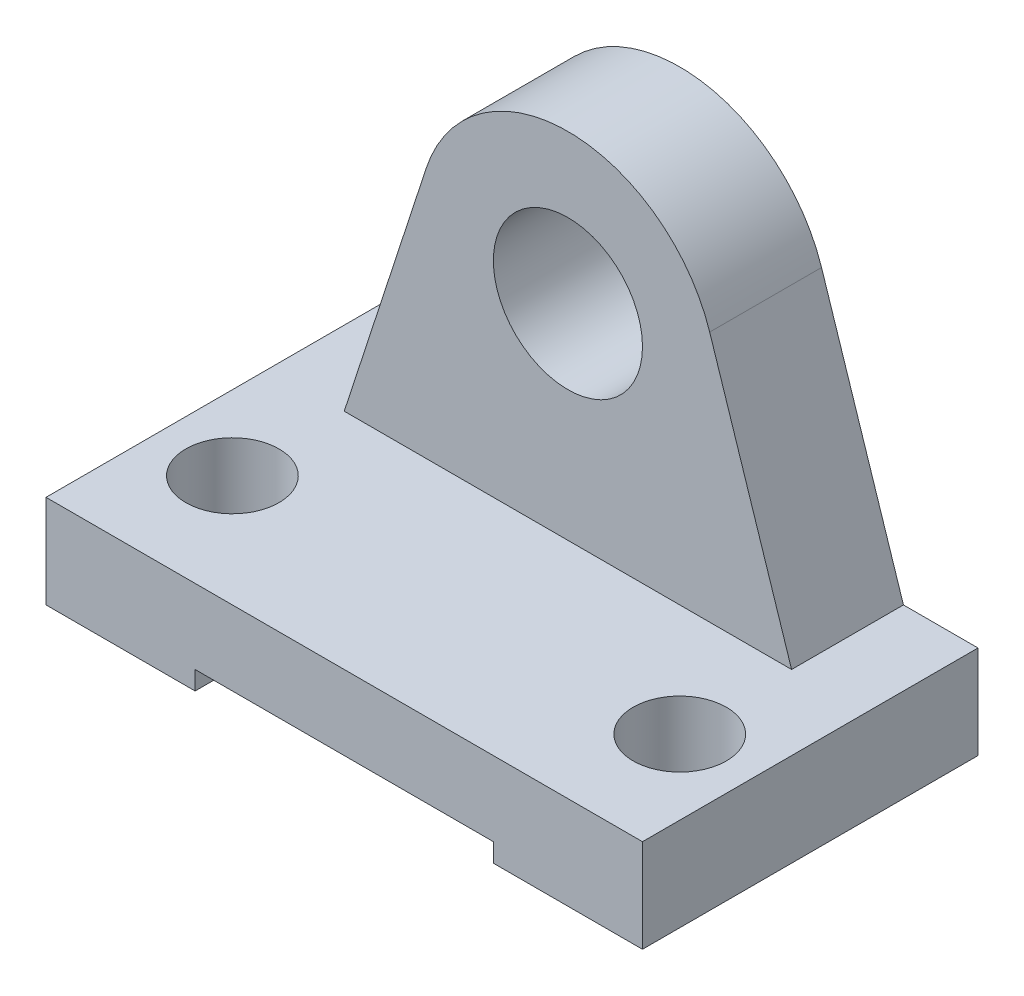
SolidWorks part; units mm, degrees
ref_plane "前视基准面" through (0, 0, 0) normal (0, 0, 1) x (1, 0, 0)
ref_plane "上视基准面" through (0, 0, 0) normal (0, 1, 0) x (1, 0, 0)
ref_plane "右视基准面" through (0, 0, 0) normal (1, 0, 0) x (0, 0, -1)
other "Configuration Table"
sketch "草图1" plane through (0, 0, 0) normal (0, 0, 1) x (1, 0, 0)
  line L0 (-415.6693, 0) -> (20367.7972, 0) construction
  line L1 (0, -415.6693) -> (0, 20367.7972) construction
  line L2 (8, 0) -> (-8, 0)
  line L3 (-8, 0) -> (-8, -1)
  line L4 (-8, -1) -> (-16, -1)
  line L5 (-16, -1) -> (-16, 4)
  line L6 (-16, 4) -> (16, 4)
  line L7 (-12, 4) -> (-7.6061, 17.4794)
  line L8 (16, -1) -> (16, 4)
  line L9 (8, -1) -> (16, -1)
  line L10 (12, 4) -> (7.6061, 17.4794)
  line L11 (8, 0) -> (8, -1)
  arc A0 (-7.6061, 17.4794) -> (7.6061, 17.4794) centre (0, 15) cw
  circle A1 centre (0, 15) radius 4
  point P17 (0, 4)
  point P20 (0, 0)
  dimension "D1" = 8
  dimension "D2" = 8
  dimension "D3" = 5
  dimension "D4" = 1
  dimension "D5" = 16
  dimension "D6" = 16
  dimension "D7" = 24
  dimension "D8" = 32
extrude "凸台-拉伸2" add sketch "草图1" along normal blind 18 contours L6 L8 L9 L11 L2 L3 L4 L5
extrude "凸台-拉伸3" add sketch "草图1<4>" along normal blind 6 contours A0 L7 L6 L10 A1 region at (0, 4.3061, 0)
sketch "草图1<4>" plane through (0, 0, 0) normal (0, 0, 1) x (1, 0, 0) same geometry as "草图1"
sketch "草图3" plane through (0, 4, 0) normal (0, 1, 0) x (1, 0, 0)
  line L0 (0, -1000) -> (0, 49000) construction
  line L1 (-16, 0) -> (-12, 0) construction
  circle A0 centre (-12, -12) radius 2.5
  circle A1 centre (12, -12) radius 2.5
  point P9 (12, -12)
  dimension "D3" = 5
  dimension "D1" = 24
  dimension "D2" = 12
extrude "切除-拉伸2" cut sketch "草图3" against normal through all contours A0 | A1
